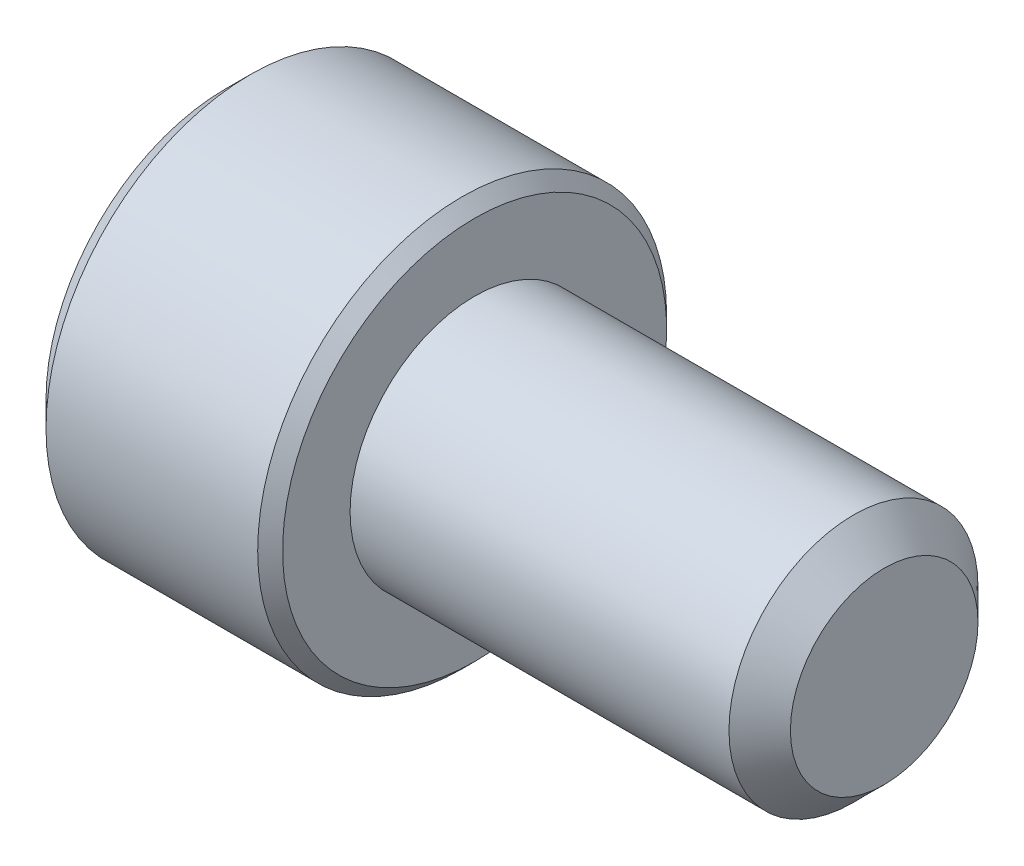
SolidWorks part; units mm, degrees
material "Alloy Steel"
ref_plane "Front Plane" through (0, 0, 0) normal (0, 0, 1) x (1, 0, 0)
ref_plane "Top Plane" through (0, 0, 0) normal (0, 1, 0) x (1, 0, 0)
ref_plane "Right Plane" through (0, 0, 0) normal (1, 0, 0) x (0, 0, -1)
sketch "Sketch1" plane through (0, 0, 0) normal (0, 0, 1) x (1, 0, 0)
  line L0 (3.9688, 0) -> (-3.9688, 0) construction
  line L1 (3.9687, 2.413) -> (3.9688, -2.413) construction
  line L2 (-3.9688, 3.7211) -> (-3.9687, -3.7211) construction
  line L3 (-4.21, 3.9624) -> (-8.3122, 3.9624) construction
  line L4 (-8.3122, 3.9624) -> (-8.7948, 3.4798) construction
  line L5 (-8.7948, 3.4798) -> (-8.7948, -3.4798) construction
  line L6 (-8.7948, -3.4798) -> (-8.3121, -3.9624) construction
  line L7 (-8.3121, -3.9624) -> (-4.21, -3.9624) construction
  line L8 (-4.21, 3.9624) -> (-3.9688, 3.7211) construction
  line L9 (-3.9687, -3.7211) -> (-4.21, -3.9624) construction
  point P5 (-3.9688, 3.9624)
  point P6 (-3.9687, -3.9624)
  point P7 (-5.8182, 0)
  point P12 (0.7938, -2.413)
  dimension "D1" = 45
  dimension "D2" = 3.175
ref_plane "Plane1" through (3.9688, 0, 0) normal (1, 0, 0) x (0, 0, -1)
ref_plane "Plane2" through (-8.7948, 0, 0) normal (1, 0, 0) x (0, 0, -1)
sketch "Sketch2" plane through (3.9688, 0, 0) normal (1, 0, 0) x (0, 0, -1)
  circle A0 centre (0, 0) radius 2.413
extrude "Boss-Extrude1" add sketch "Sketch2" against normal up to vertex (7.9375 mm away) up to point (-3.9688, 0, 0)
sketch "Sketch3" plane through (3.9688, 0, 0) normal (1, 0, 0) x (0, 0, -1)
  circle A0 centre (0, 0) radius 2.413 construction
  circle A1 centre (0, 0) radius 2.413
curve "Helix/Spiral1" pitch 0.7937 height 8.7312 turns 11 parameters "Pitch"=0.7937
chamfer "Chamfer1" distance 0.5953 angle 45 1 edges at (3.9688, 0, -2.413)
sketch "Sketch5" plane through (0, 0, 0) normal (0, 0, 1) x (1, 0, 0)
  line L0 (3.6215, 2.413) -> (4.316, 2.413)
  line L1 (4.316, 2.413) -> (4.0184, 1.8974)
  line L2 (4.0184, 1.8974) -> (3.9191, 1.8974)
  line L3 (3.9191, 1.8974) -> (3.6215, 2.413)
  line L4 (3.9687, 1.8974) -> (3.9687, 2.413) construction
  line L5 (3.7703, 2.1552) -> (4.1672, 2.1552) construction
  dimension "D1" = 60
  dimension "D2" = 0.3969
  dimension "D3" = 0.0992
sweep "Cut-Sweep1" [suppressed] cut profiles "Sketch5" path "Helix/Spiral1"
sketch "Sketch4" plane through (-8.7948, 0, 0) normal (1, 0, 0) x (0, 0, -1)
  line L0 (-3.9624, 0.7937) -> (3.9624, 0.7937) construction
  line L1 (0, 2.2914) -> (-1.9844, 1.1457)
  line L2 (-1.9844, 1.1457) -> (-1.9844, -1.1457)
  line L3 (-1.9844, -1.1457) -> (0, -2.2914)
  line L4 (0, -2.2914) -> (1.9844, -1.1457)
  line L5 (1.9844, -1.1457) -> (1.9844, 1.1457)
  line L6 (1.9844, 1.1457) -> (0, 2.2914)
  line L7 (0, 0) -> (0, 0.7937) construction
  circle A0 centre (0, 0) radius 1.9844 construction
  dimension "D2" = 0.7937
sketch "Sketch6" plane through (0, 0, 0) normal (0, 0, 1) x (1, 0, 0)
  line L0 (-8.3122, 3.9624) -> (-8.7948, 3.4798) construction
  line L2 (-3.9688, 3.7211) -> (-3.9687, -3.7211) construction
  line L3 (-8.7948, 3.4798) -> (-8.7948, -3.4798) construction
  line L4 (-8.3122, 3.9624) -> (-8.7948, 3.4798)
  line L5 (-4.21, 3.9624) -> (-8.3122, 3.9624) construction
  line L6 (-3.9688, 3.7211) -> (-3.9688, 0)
  line L7 (-8.7948, 3.4798) -> (-8.7948, 0)
  line L8 (-3.9688, 0) -> (-8.7948, 0) construction
  line L9 (-3.9688, 0) -> (-8.7948, 0)
  line L10 (-4.21, 3.9624) -> (-3.9688, 3.7211) construction
  line L11 (-4.21, 3.9624) -> (-8.3122, 3.9624)
  line L12 (-4.21, 3.9624) -> (-3.9688, 3.7211)
revolve "Revolve1" add sketch "Sketch6" angle 360 about L8
extrude "Cut-Extrude1" cut sketch "Sketch4" along normal up to vertex (2.9766 mm away) up to point (-5.8182, 0, 0)
sketch "Sketch8" plane through (-8.7948, 0, 0) normal (-1, 0, 0) x (0, 0, 1)
  circle A1 centre (0, 0) radius 2.2914
extrude "Cut-Extrude2" cut sketch "Sketch8" against normal blind 0.9652 draft 45
equation "\"D3@Helix/Spiral1\" = \"Length@Sketch1\"+\"Pitch@Helix/Spiral1\""
equation "\"D3@Sketch5\" = \"Pitch@Helix/Spiral1\"*.125"
equation "\"D2@Sketch5\" = \"Pitch@Helix/Spiral1\"*.50"
equation "\"D1@Chamfer1\" = \"Pitch@Helix/Spiral1\"*.75"
equation "\"D2@Sketch1\" = \"Pitch@Helix/Spiral1\"*4"
equation "\"D1@Sketch4\" = \"Head Dia@Sketch1\""
equation "\"Chamfer@Sketch1\" = \"Head Height@Sketch1\"/10"
equation "\"D3@Sketch1\" = \"Chamfer@Sketch1\"/2"
equation "\"D1@Cut-Extrude2\" = \"Chamfer@Sketch1\"*2"
